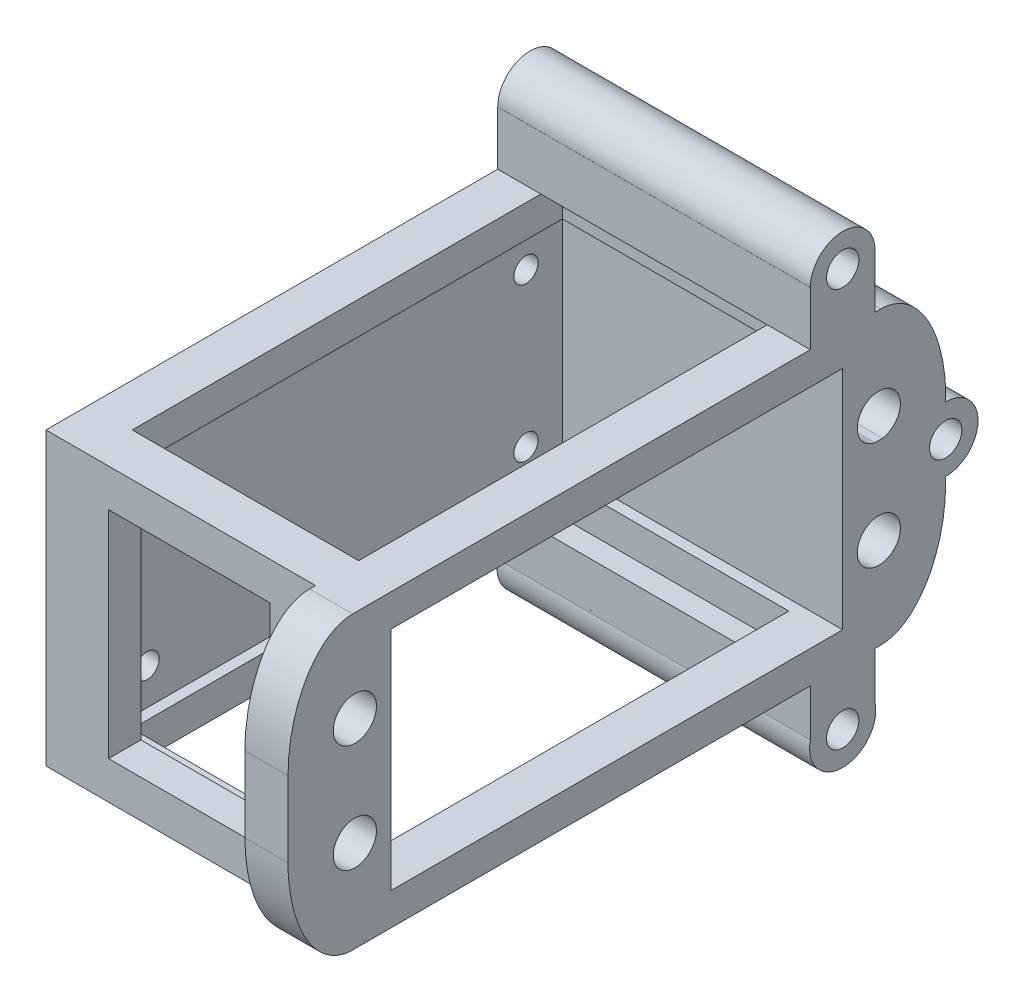
SolidWorks part; units mm, degrees
ref_plane "Front Plane" through (0, 0, 0) normal (0, 0, 1) x (1, 0, 0)
ref_plane "Top Plane" through (0, 0, 0) normal (0, 1, 0) x (1, 0, 0)
ref_plane "Right Plane" through (0, 0, 0) normal (1, 0, 0) x (0, 0, -1)
sketch "Sketch1" plane through (0, 0, 0) normal (1, 0, 0) x (0, 0, -1)
  line L1 (-3, 24) -> (44.9, 24)
  line L6 (0, 0) -> (41.9, 0)
  line L7 (0, 0) -> (0, 21)
  line L8 (0, 21) -> (41.9, 21)
  line L9 (41.9, 0) -> (41.9, 21)
  line L10 (44.9, -3) -> (44.9, 24)
  line L11 (-3, -3) -> (44.9, -3)
  line L12 (-3, -3) -> (-3, 24)
  circle A0 centre (3.38, 3.38) radius 1.125
  circle A1 centre (3.38, 17.62) radius 1.125
  circle A2 centre (38.52, 3.38) radius 1.125
  circle A3 centre (38.52, 17.62) radius 1.125
  dimension "D4" = 3
  dimension "D7" = 3.38
  dimension "D8" = 3.38
  dimension "D9" = 3.38
  dimension "D10" = 3.38
  dimension "D11" = 3.38
  dimension "D12" = 3.38
  dimension "D5" = 3.38
  dimension "D6" = 3.38
  dimension "D1" = 41.9
  dimension "D2" = 21
  dimension "D3" = 3
extrude "Boss-Extrude1" add sketch "Sketch1" along normal blind 3 contours L6 L9 L8 L7 A3 A2 A1 A0 region at (0, 10.5, -20.95)
extrude "Boss-Extrude2" add sketch "Sketch1<3>" along normal blind 29 contours L12 L11 L10 L1 L9 L6 L7 L8 region at (0, 23.4501, -20.95)
sketch "Sketch1<3>" plane through (0, 0, 0) normal (1, 0, 0) x (0, 0, -1) same geometry as "Sketch1"
sketch "Sketch2" plane through (0, 0, 3) normal (0, 0, 1) x (1, 0, 0)
  line L0 (29, 24) -> (0, 24) construction
  line L1 (20.8, 20.5) -> (5.8, 20.5)
  line L2 (20.8, 20.5) -> (20.8, 0.5)
  line L3 (20.8, 0.5) -> (5.8, 0.5)
  line L4 (5.8, 20.5) -> (5.8, 0.5)
  line L5 (0, -3) -> (0, 24) construction
  dimension "D1" = 20
  dimension "D2" = 3.5
  dimension "D3" = 15
  dimension "D4" = 5.8
extrude "Cut-Extrude1" cut sketch "Sketch2" against normal up to next
sketch "Sketch4" plane through (0, -3, 0) normal (0, -1, 0) x (1, 0, 0)
  line L0 (29, 3) -> (0, 3) construction
  line L1 (4, -1) -> (25, -1)
  line L2 (4, -1) -> (4, -40.9)
  line L3 (4, -40.9) -> (25, -40.9)
  line L4 (25, -1) -> (25, -40.9)
  line L5 (29, 3) -> (29, -44.9) construction
  line L6 (0, 3) -> (0, -44.9) construction
  line L7 (29, -44.9) -> (0, -44.9) construction
  dimension "D1" = 4
  dimension "D2" = 4
  dimension "D3" = 4
  dimension "D4" = 4
extrude "Cut-Extrude2" cut sketch "Sketch4" against normal blind 35
sketch "Sketch5" plane through (0, 0, 0) normal (-1, 0, 0) x (0, 0, 1)
  line L1 (3, 24) -> (-44.9, 24) construction
  line L2 (3, -3) -> (3, 24) construction
  circle A0 centre (-10.5, 10.5) radius 4
  dimension "D2" = 8
  dimension "D3" = 13.5
  dimension "D1" = 13.5
extrude "Boss-Extrude3" add sketch "Sketch5" along normal blind 4
sketch "Sketch6" plane through (0, 0, -44.9) normal (0, 0, -1) x (-1, 0, 0)
  line L0 (-29, 24) -> (0, 24) construction
  line L1 (-29, -3) -> (-25, -3)
  line L2 (-29, -3) -> (-29, 24)
  line L3 (-29, 24) -> (-25, 24)
  line L4 (-25, -3) -> (-25, 24)
  dimension "D1" = 4
extrude "Boss-Extrude4" add sketch "Sketch6" along normal blind 6.55
sketch "Sketch7" plane through (0, 0, 3) normal (0, 0, 1) x (1, 0, 0)
  line L0 (29, -3) -> (0, -3) construction
  line L1 (29, 24) -> (25, 24)
  line L2 (29, 24) -> (29, -3)
  line L3 (29, -3) -> (25, -3)
  line L4 (25, 24) -> (25, -3)
  dimension "D1" = 4
extrude "Boss-Extrude5" add sketch "Sketch7" along normal blind 6.55
sketch "Sketch10" plane through (29, 0, 0) normal (1, 0, 0) x (0, 0, -1)
  line L0 (-9.55, 24) -> (51.45, 24) construction
  line L1 (0, 0) -> (0, 21) construction
  line L2 (0, 0) -> (0, 21) construction
  line L3 (41.9, 0) -> (41.9, 21) construction
  circle A0 centre (-3.35, 15.5) radius 2
  circle A1 centre (-3.35, 5.5) radius 2
  circle A2 centre (45.25, 5.5) radius 2
  circle A3 centre (45.25, 15.5) radius 2
  dimension "D1" = 4
  dimension "D2" = 10
  dimension "D3" = 8.5
  dimension "D4" = 10
  dimension "D5" = 3.35
  dimension "D6" = 3.35
  dimension "D7" = 3.35
  dimension "D8" = 3.35
  dimension "D9" = 8.5
extrude "Cut-Extrude3" cut sketch "Sketch10" against normal up to next
sketch "Sketch11" plane through (0, 0, 0) normal (-1, 0, 0) x (0, 0, 1)
  line L1 (-44.9, 7.4691) -> (-44.9, 13.5309) construction
  line L2 (-44.9, 24) -> (-38.9, 24)
  line L3 (-44.9, 24) -> (-44.9, 29)
  line L4 (-44.9, 29) -> (-38.9, 29)
  line L5 (-38.9, 24) -> (-38.9, 29)
  line L6 (-44.9, 13.5309) -> (-51.45, 13.5309)
  line L7 (-44.9, 13.5309) -> (-44.9, 7.5309)
  line L8 (-44.9, 7.5309) -> (-51.45, 7.5309)
  line L9 (-51.45, 13.5309) -> (-51.45, 7.5309)
  line L10 (-51.45, -3) -> (-51.45, 24) construction
  line L11 (3, -3) -> (-44.9, -3) construction
  line L12 (-44.9, -3) -> (-38.9, -3)
  line L13 (-44.9, -3) -> (-44.9, -8)
  line L14 (-44.9, -8) -> (-38.9, -8)
  line L15 (-38.9, -3) -> (-38.9, -8)
  circle A1 centre (-41.9, 29) radius 2.9964
  circle A2 centre (-51.45, 10.5309) radius 3
  circle A3 centre (-41.9, -8) radius 3.0678
  circle A4 centre (-41.9, 29) radius 1.5
  circle A5 centre (-41.9, -8) radius 1.5
  circle A6 centre (-51.45, 10.5309) radius 1.5
  line M13 (-44.9, 13.5309) -> (-44.9, 7.4691)
  line M16 (-44.9, -3) -> (3, -3)
  line M18 (3, 24) -> (-44.9, 24)
  dimension "D1" = 6
  dimension "D2" = 6
  dimension "D7" = 3
  dimension "D8" = 3
  dimension "D9" = 3
  dimension "D3" = 6
  dimension "D4" = 5
  dimension "D5" = 5
  dimension "D6" = 0
extrude "Boss-Extrude10" add sketch "Sketch11" against normal up to surface (29 mm away) contours A2 L8 L6 M13 | L9 A2 | L9 A2 | L4 A1 | A1 L4 L3 L5 M18 | L4 A1 | L15 A3 L13 L14 | L13 A3 L15 L14 | A3 L15 L13 M16 region at (0, 25.4103, -41.9) region at (0, 31.9294, -41.9) region at (0, 28.933, -44.1482) region at (0, 10.5309, -47.0504) region at (0, 12.6047, -49.3761) region at (0, 12.7809, -51.5171) region at (0, -4.3491, -41.9) region at (0, -6.4823, -41.9) region at (0, -9.5021, -41.9) up to face at (29, 15.5, -47.25)
fillet "Fillet3" radius 6 4 edges at (27, 24, 9.55) (27, -3, 9.55) (27, 24, -51.45) (27, -3, -51.45) second distance 10 first distance on face at (16.6, 24, -13.25) first distance on face at (16.6, -3, -13.25) first distance on face at (27, 24, -48.175) first distance on face at (27, -3, -48.175)
sketch "Sketch12" plane through (29, 0, 0) normal (1, 0, 0) x (0, 0, -1)
  line L0 (51.45, 12.0309) -> (51.45, 9.0309) construction
  circle A0 centre (51.45, 10.5309) radius 1.5
  dimension "D1" = 3
extrude "Cut-Extrude4" cut sketch "Sketch12" against normal up to next
